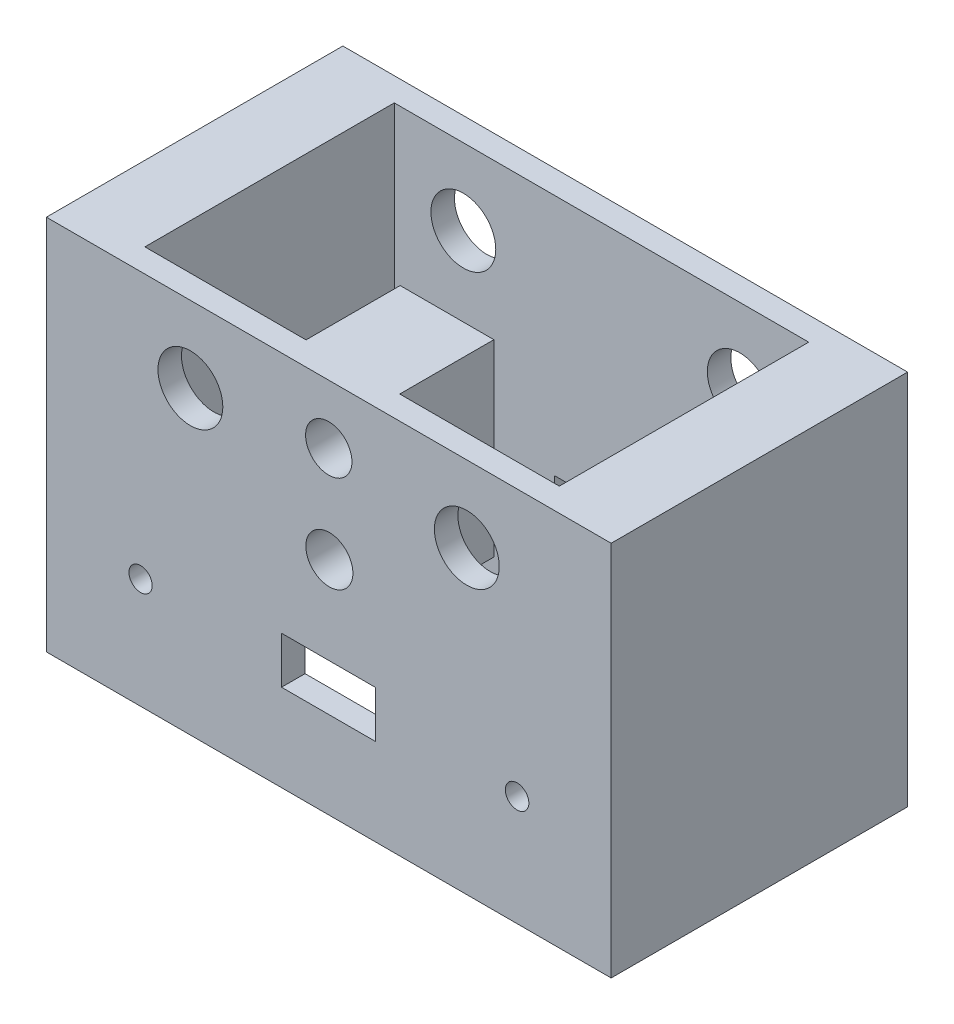
SolidWorks part; units mm, degrees
ref_plane "Front Plane" through (0, 0, 0) normal (0, 0, 1) x (1, 0, 0)
ref_plane "Top Plane" through (0, 0, 0) normal (0, 1, 0) x (1, 0, 0)
ref_plane "Right Plane" through (0, 0, 0) normal (1, 0, 0) x (0, 0, -1)
sketch "Sketch2" plane through (0, 0, 0) normal (0, 0, 1) x (1, 0, 0)
  line L0 (-38.9521, 81.0614) -> (0, 81.0614)
  line L1 (-152.4, 101.6) -> (0, 101.6)
  line L2 (-152.4, 101.6) -> (-152.4, 0)
  line L3 (-152.4, 0) -> (0, 0)
  line L4 (0, 101.6) -> (0, 0)
  line L9 (-113.538, 81.0614) -> (-152.4, 81.0614)
  line L10 (-76.1845, 9.2391) -> (-76.1845, 50.2517)
  line L11 (-130.1267, 29.7454) -> (-130.1267, 9.2391)
  line L12 (-22.2095, 29.7454) -> (-22.2095, 9.4254)
  line L13 (-48.8795, 29.7454) -> (-103.4895, 29.7454) construction
  line L14 (-48.8795, 9.4254) -> (-103.4895, 9.4254)
  line L15 (-48.8795, 50.0654) -> (-103.4895, 50.0654)
  line L17 (-22.2095, 29.7454) -> (-22.2095, 50.0654)
  line L19 (-130.1267, 9.2391) -> (-22.2095, 9.2391)
  line L20 (-130.1267, 9.2391) -> (-130.1267, 50.0654)
  line L21 (-130.1267, 50.0654) -> (-22.2095, 50.0654)
  line L22 (-22.2095, 9.2391) -> (-22.2095, 50.0654)
  line L23 (-88.9468, 29.7454) -> (-88.9468, 36.1065)
  line L24 (-88.9468, 36.1065) -> (-63.5515, 36.1065)
  line L25 (-63.5515, 36.1065) -> (-63.5515, 23.477)
  line L26 (-63.5515, 23.477) -> (-88.9468, 23.477)
  line L27 (-88.9468, 23.477) -> (-88.9468, 29.7454)
  circle A0 centre (-113.538, 81.0614) radius 8.75
  circle A1 centre (-38.9521, 81.0614) radius 8.75
  circle A2 centre (-25.3845, 29.7454) radius 3.175
  circle A3 centre (-126.9845, 29.7454) radius 3.1422
  arc A4 (-48.8795, 9.4254) -> (-48.8795, 50.0654) centre (-48.8795, 29.7454) ccw
  arc A5 (-103.4895, 50.0654) -> (-103.4895, 9.4254) centre (-103.4895, 29.7454) ccw
  point P26 (-76.1845, 29.7454)
  dimension "D5" = 17.5
  dimension "D6" = 17.5
  dimension "D10" = 6.35
  dimension "D11" = 20.32
  dimension "D1" = 152.4
  dimension "D2" = 101.6
  dimension "D7" = 38.9521
  dimension "D8" = 38.862
  dimension "D12" = 54.61
extrude "Boss-Extrude1" add sketch "Sketch2" along normal blind 80.0001 contours A1 L4 L1 L2 A0 L3 L22 L19 L11 L20 L21 L15 L17 L12 | L15 A5 L14 L10 | A4 L15 L10 L14 | A5 L21 L20 A3 L11 L19 L10 L14 | A4 L14 L10 L19 L22 L12 A2 | A4 A2 L17 L21 region at (-76.2112, 58.2188, 0) region at (-103.1556, 9.3068, 0) region at (-29.741, 16.0891, 0) region at (-99.6175, 29.7407, 0) region at (-52.7624, 29.7408, 0) region at (-28.7715, 43.065, 0)
sketch "Sketch3" plane through (0, 101.6, 0) normal (0, 1, 0) x (1, 0, 0)
  line L0 (-76.2, 0) -> (-76.2, -6.35)
  line L1 (-152.4, 0) -> (0, 0) construction
  line L2 (-76.2, -80.0001) -> (-76.2, -73.6501)
  line L4 (-152.4, -80.0001) -> (0, -80.0001) construction
  line L9 (-76.2, -73.6501) -> (-132.171, -73.6501)
  line L10 (-76.2, -73.6501) -> (-20.3348, -73.6501)
  line L11 (-76.2, -6.35) -> (-132.171, -6.35)
  line L12 (-76.2, -6.35) -> (-20.3348, -6.35)
  line L13 (-132.171, -73.6501) -> (-132.171, -6.35)
  line L14 (-20.3348, -6.35) -> (-20.3348, -73.6501)
  dimension "D1" = 6.35
extrude "Cut-Extrude2" cut sketch "Sketch3" against normal blind 179.8221 contours L14 L12 L11 L13 L9 L10 region at (-76.2529, 101.6, 40)
sketch "Sketch6" plane through (0, 0, 73.6501) normal (0, 0, -1) x (-1, 0, 0)
  line L0 (76.2, 101.6) -> (63.3976, 101.6)
  line L1 (152.4, 101.6) -> (0, 101.6) construction
  line L2 (63.3976, 101.6) -> (63.3976, 50.8)
  line L3 (63.3976, 50.8) -> (88.685, 50.8)
  line L4 (88.685, 50.8) -> (88.685, 101.6)
  line L5 (88.685, 101.6) -> (76.2, 101.6)
  circle A0 centre (76.0413, 59.7405) radius 6.35
  circle A1 centre (76.2, 85.6628) radius 6.2488
  dimension "D1" = 50.8
extrude "Cut-Extrude6" cut sketch "Sketch6" against normal blind 41.402 contours A0 | A1 region at (-76.0413, 59.7405, 73.6501)
extrude "Boss-Extrude4" add sketch "Sketch6<10>" along normal blind 25.4
sketch "Sketch6<10>" plane through (0, 0, 73.6501) normal (0, 0, -1) x (-1, 0, 0) same geometry as "Sketch6"
